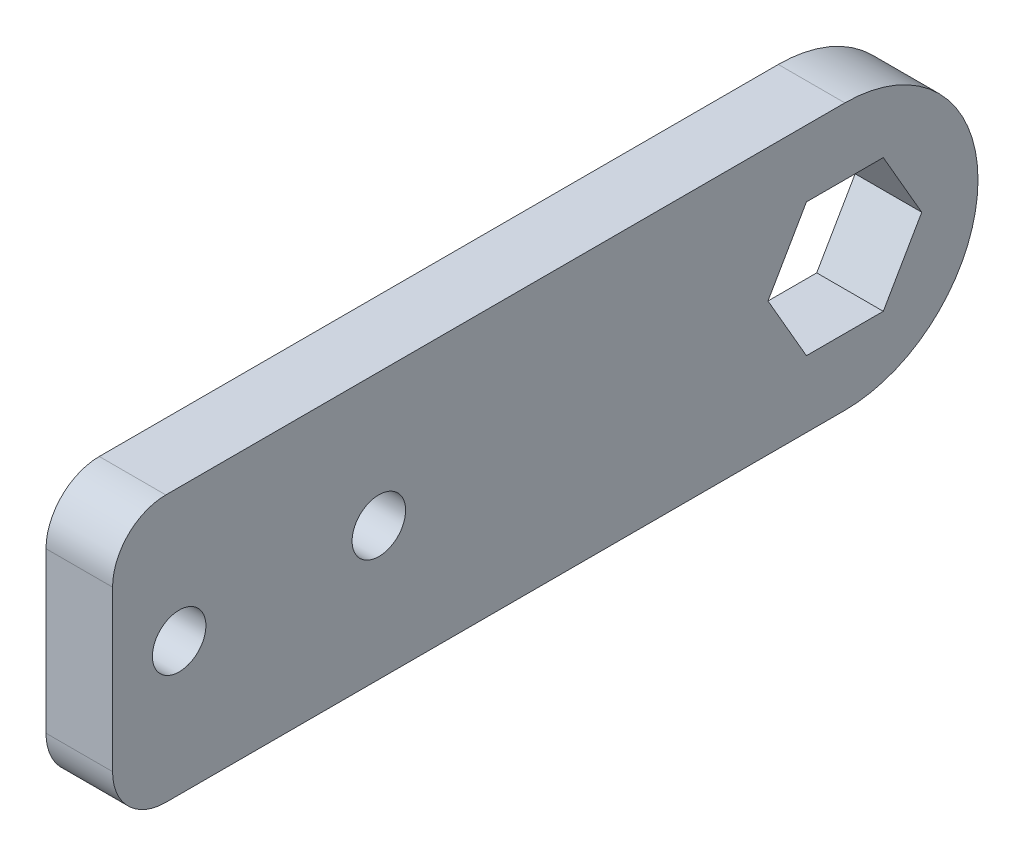
SolidWorks part; units mm, degrees
material "5052-O"
ref_plane "Front Plane" through (0, 0, 0) normal (0, 0, 1) x (1, 0, 0)
ref_plane "Top Plane" through (0, 0, 0) normal (0, 1, 0) x (1, 0, 0)
ref_plane "Right Plane" through (0, 0, 0) normal (1, 0, 0) x (0, 0, -1)
sketch "Sketch1" plane through (0, 0, 0) normal (1, 0, 0) x (0, 0, -1)
  line L1 (-41.275, -12.7) -> (41.275, -12.7)
  line L2 (-41.275, -12.7) -> (-41.275, 12.7)
  line L3 (-41.275, 12.7) -> (41.275, 12.7)
  line L4 (41.275, -12.7) -> (41.275, 12.7)
  line L5 (-41.275, -12.7) -> (41.275, 12.7) construction
  line L6 (-41.275, 12.7) -> (41.275, -12.7) construction
  point P0 (0, 0)
  dimension "D1" = 25.4
  dimension "D2" = 82.55
extrude "Boss-Extrude1" add sketch "Sketch1" along normal mid plane 6.35
fillet "Fillet1" radius 12.7 2 edges at (0, -12.7, -41.275) (0, 12.7, -41.275)
hole_wizard "#10 Clearance Hole1" positions "Sketch3" profile "Sketch5" hole size "#10" standard "ANSI Inch" end condition through all
sketch "Sketch3" plane through (3.175, 6.2729, 168.827) normal (1, 0, 0) x (0, 0, -1)
  line L0 (127.552, 6.4271) -> (127.552, -18.9729) construction
  point P0 (152.952, -6.2729)
  point P3 (133.902, -6.2729)
  point P8 (127.552, -6.2729)
  dimension "D1" = 19.05
  dimension "D2" = 6.35
sketch "Sketch5" plane through (3.175, 0, 15.875) normal (0, 1, 0) x (0, 0, -1)
  line L0 (0, 0) -> (0, 6.35)
  line L1 (0, 6.35) -> (2.5527, 6.35)
  line L2 (2.5527, 6.35) -> (2.5527, 0)
  line L5 (2.5527, 0) -> (0, 0)
  line L11 (0, -6.35) -> (0, 107.95) construction
  dimension "Thru Hole Dia." = 5.1054
  dimension "Thru Hole Depth" = 6.35
fillet "Fillet2" radius 5.08 2 edges at (0, -12.7, 41.275) (0, 12.7, 41.275)
sketch "Sketch7" plane through (3.175, 0, 0) normal (1, 0, 0) x (0, 0, -1)
  line L1 (32.2412, 6.35) -> (24.9088, 6.35)
  line L2 (24.9088, 6.35) -> (21.2427, 0)
  line L3 (21.2427, 0) -> (24.9088, -6.35)
  line L4 (24.9088, -6.35) -> (32.2412, -6.35)
  line L5 (32.2412, -6.35) -> (35.9073, 0)
  line L6 (35.9073, 0) -> (32.2412, 6.35)
  circle A1 centre (28.575, 0) radius 6.35 construction
  arc A3 (41.275, 0) -> (28.575, 12.7) centre (28.575, 0) ccw construction
  dimension "D1" = 12.7
extrude "Cut-Extrude1" cut sketch "Sketch7" against normal through all
